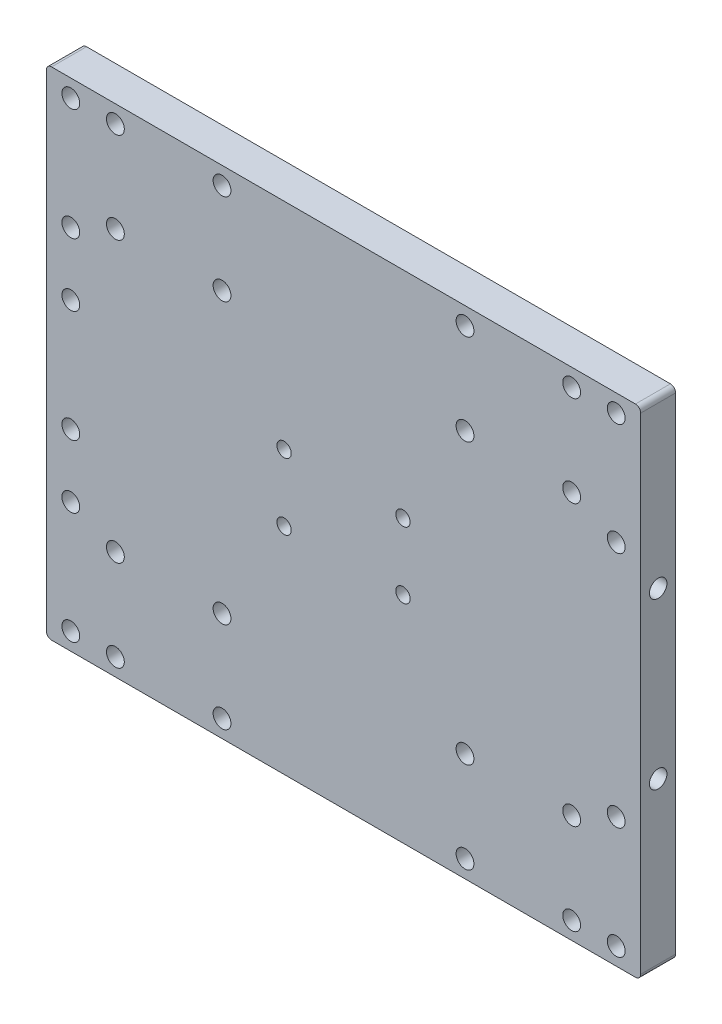
SolidWorks part; units mm, degrees
ref_plane "Front Plane" through (0, 0, 0) normal (0, 0, 1) x (1, 0, 0)
ref_plane "Top Plane" through (0, 0, 0) normal (0, 1, 0) x (1, 0, 0)
ref_plane "Right Plane" through (0, 0, 0) normal (1, 0, 0) x (0, 0, -1)
sketch "Sketch1" plane through (0, 0, 0) normal (0, 0, 1) x (1, 0, 0)
  line L1 (85, -71) -> (-85, -71)
  line L2 (85, -71) -> (85, 71)
  line L3 (85, 71) -> (-85, 71)
  line L4 (-85, -71) -> (-85, 71)
  line L5 (85, -71) -> (-85, 71) construction
  line L6 (85, 71) -> (-85, -71) construction
  point P0 (0, 0)
  dimension "D1" = 170
  dimension "D2" = 142
extrude "Boss-Extrude1" add sketch "Sketch1" along normal mid plane 10
sketch "Sketch2" plane through (0, 0, 5) normal (0, 0, 1) x (1, 0, 0)
  line L0 (-65.25, 71) -> (-65.25, -71) construction
  line L1 (65.25, -71) -> (65.25, 71) construction
  line L2 (-34.75, 71) -> (-34.75, -71) construction
  line L3 (34.75, -71) -> (34.75, 71) construction
  line L4 (70.6711, 66) -> (-71.3289, 66) construction
  line L5 (-71.3289, -66) -> (70.6711, -66) construction
  line L6 (70.6711, 40) -> (-71.3289, 40) construction
  line L7 (-71.3289, -40) -> (70.6711, -40) construction
  line L8 (85, 71) -> (-85, 71) construction
  line L9 (-85, -71) -> (85, -71) construction
  line L10 (-85, 71) -> (-85, -71) construction
  line L11 (85, -71) -> (85, 71) construction
  circle A0 centre (-65.25, 66) radius 2.55
  circle A1 centre (-34.75, 66) radius 2.55
  circle A2 centre (-34.75, 40) radius 2.55
  circle A3 centre (-65.25, 40) radius 2.55
  circle A4 centre (65.25, 66) radius 2.55
  circle A5 centre (65.25, 40) radius 2.55
  circle A6 centre (34.75, 40) radius 2.55
  circle A7 centre (34.75, 66) radius 2.55
  circle A8 centre (-65.25, -40) radius 2.55
  circle A9 centre (-34.75, -40) radius 2.55
  circle A10 centre (-34.75, -66) radius 2.55
  circle A11 centre (-65.25, -66) radius 2.55
  circle A12 centre (34.75, -40) radius 2.55
  circle A13 centre (65.25, -40) radius 2.55
  circle A14 centre (65.25, -66) radius 2.55
  circle A15 centre (34.75, -66) radius 2.55
  dimension "D1" = 5.1
  dimension "D2" = 5.1
  dimension "D3" = 5.1
  dimension "D4" = 5.1
  dimension "D5" = 5.1
  dimension "D6" = 5.1
  dimension "D7" = 5.1
  dimension "D8" = 5.1
  dimension "D9" = 5.1
  dimension "D10" = 5.1
  dimension "D11" = 5.1
  dimension "D12" = 5.1
  dimension "D13" = 5.1
  dimension "D14" = 5.1
  dimension "D15" = 5.1
  dimension "D16" = 5.1
  dimension "D17" = 5
  dimension "D18" = 5
  dimension "D19" = 26
  dimension "D20" = 26
  dimension "D21" = 30.5
  dimension "D22" = 30.5
  dimension "D23" = 19.75
  dimension "D24" = 19.75
extrude "Cut-Extrude1" cut sketch "Sketch2" against normal through all
sketch "Sketch3" plane through (0, 0, 5) normal (0, 0, 1) x (1, 0, 0)
  line L0 (-78, 71) -> (-78, -71) construction
  line L1 (85, 71) -> (-85, 71) construction
  line L2 (-85, -71) -> (85, -71) construction
  line L3 (78, 71) -> (78, -71) construction
  line L4 (-85, 66) -> (85, 66) construction
  line L5 (-85, 71) -> (-85, -71) construction
  line L6 (85, -71) -> (85, 71) construction
  line L7 (-85, 34) -> (85, 34) construction
  line L8 (-85, -34) -> (85, -34) construction
  line L9 (-85, -66) -> (85, -66) construction
  circle A0 centre (-78, 66) radius 2.55
  circle A1 centre (-78, 34) radius 2.55
  circle A2 centre (-78, -34) radius 2.55
  circle A3 centre (-78, -66) radius 2.55
  circle A4 centre (78, 66) radius 2.55
  circle A5 centre (78, 34) radius 2.55
  circle A6 centre (78, -34) radius 2.55
  circle A7 centre (78, -66) radius 2.55
  dimension "D7" = 5.1
  dimension "D8" = 5.1
  dimension "D9" = 5.1
  dimension "D10" = 5.1
  dimension "D11" = 5.1
  dimension "D12" = 5.1
  dimension "D13" = 5.1
  dimension "D14" = 5.1
  dimension "D1" = 5
  dimension "D2" = 32
  dimension "D3" = 5
  dimension "D4" = 32
  dimension "D5" = 7
  dimension "D6" = 7
extrude "Cut-Extrude2" cut sketch "Sketch3" against normal through all
sketch "Sketch4" plane through (0, 0, 5) normal (0, 0, 1) x (1, 0, 0)
  line L1 (-17, -9.5) -> (17, -9.5) construction
  line L2 (-17, -9.5) -> (-17, 9.5) construction
  line L3 (-17, 9.5) -> (17, 9.5) construction
  line L4 (17, -9.5) -> (17, 9.5) construction
  line L5 (-17, -9.5) -> (17, 9.5) construction
  line L6 (-17, 9.5) -> (17, -9.5) construction
  circle A0 centre (-17, 9.5) radius 2.05
  circle A1 centre (-17, -9.5) radius 2.05
  circle A2 centre (17, -9.5) radius 2.05
  circle A3 centre (17, 9.5) radius 2.05
  point P0 (0, 0)
  dimension "D3" = 4.1
  dimension "D4" = 4.1
  dimension "D5" = 4.1
  dimension "D6" = 4.1
  dimension "D1" = 34
  dimension "D2" = 19
extrude "Cut-Extrude3" cut sketch "Sketch4" against normal through all
sketch "Sketch5" plane through (85, 0, 0) normal (1, 0, 0) x (0, 0, -1)
  line L0 (0, 71) -> (0, -71) construction
  line L1 (-5, 71) -> (5, 71) construction
  line L2 (-5, -71) -> (5, -71) construction
  circle A0 centre (0, 23.6) radius 2.5
  circle A1 centre (0, -23.6) radius 2.5
  dimension "D1" = 5
  dimension "D2" = 5
  dimension "D3" = 23.6
  dimension "D4" = 23.6
extrude "Cut-Extrude4" cut sketch "Sketch5" against normal blind 10
sketch "Sketch6" plane through (0, 0, 5) normal (0, 0, 1) x (1, 0, 0)
  line L0 (-78, 34) -> (-78, -34) construction
  line L1 (-78, 0) -> (-85, 0) construction
  line L2 (-85, 71) -> (-85, -71) construction
  circle A0 centre (-78, 16) radius 2.55
  circle A1 centre (-78, -16) radius 2.55
  dimension "D1" = 5.1
  dimension "D2" = 5.1
  dimension "D3" = 16
  dimension "D4" = 16
extrude "Cut-Extrude5" cut sketch "Sketch6" against normal through all
fillet "Fillet1" radius 1.5 4 edges at (-85, -71, 0) (85, -71, 0) (85, 71, 0) (-85, 71, 0)
equation "\"D23@Sketch2\"=5.75+14"
equation "\"D24@Sketch2\"=5.75+14"
equation "\"D6@Sketch4\"=\"D3@Sketch4\""
equation "\"D4@Sketch4\"=\"D3@Sketch4\""
equation "\"D5@Sketch4\"=\"D3@Sketch4\""
equation "\"D3@Sketch5\"=47.2/2"
equation "\"D4@Sketch5\"=47.2/2"
equation "\"D3@Sketch6\"=32/2"
equation "\"D4@Sketch6\"=32/2"
equation "\"D8@Sketch3\"=\"D7@Sketch3\""
equation "\"D9@Sketch3\"=\"D7@Sketch3\""
equation "\"D10@Sketch3\"=\"D7@Sketch3\""
equation "\"D11@Sketch3\"=\"D7@Sketch3\""
equation "\"D12@Sketch3\"=\"D7@Sketch3\""
equation "\"D13@Sketch3\"=\"D7@Sketch3\""
equation "\"D14@Sketch3\"=\"D7@Sketch3\""
equation "\"D1@Sketch6\"=\"D2@Sketch6\""
